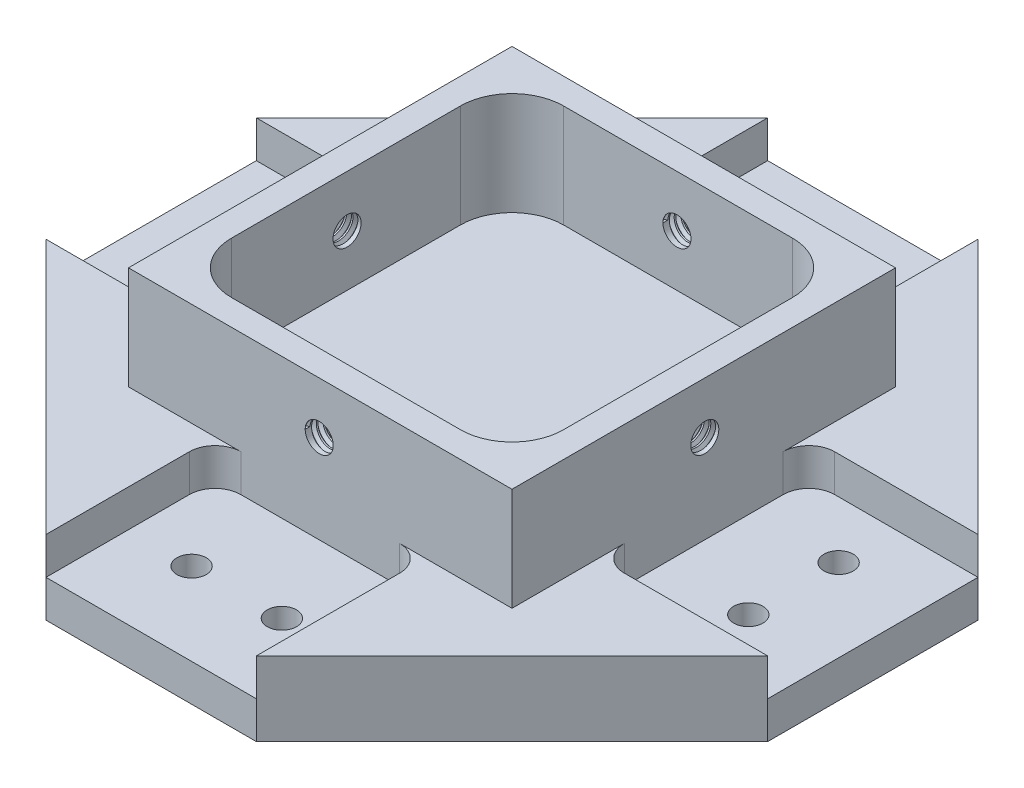
SolidWorks part; units mm, degrees
material "6061 Alloy"
ref_plane "Front Plane" through (0, 0, 0) normal (0, 0, 1) x (1, 0, 0)
ref_plane "Top Plane" through (0, 0, 0) normal (0, 1, 0) x (1, 0, 0)
ref_plane "Right Plane" through (0, 0, 0) normal (1, 0, 0) x (0, 0, -1)
sketch "Sketch1" plane through (0, 0, 0) normal (0, 1, 0) x (1, 0, 0)
  line L1 (0, 0) -> (88.9, 0)
  line L2 (0, 0) -> (0, 88.9)
  line L3 (0, 88.9) -> (88.9, 88.9)
  line L4 (88.9, 0) -> (88.9, 88.9)
  dimension "D1" = 88.9
  dimension "D2" = 88.9
extrude "Boss-Extrude1" add sketch "Sketch1" along normal blind 9.144
sketch "Sketch2" plane through (0, 9.144, 0) normal (0, 1, 0) x (1, 0, 0)
  line L0 (88.9, 88.9) -> (0, 88.9) construction
  line L1 (31.496, 88.9) -> (57.404, 88.9)
  line L2 (31.496, 88.9) -> (31.496, 67.31)
  line L3 (31.496, 67.31) -> (57.404, 67.31)
  line L4 (57.404, 88.9) -> (57.404, 67.31)
  line L5 (0, 88.9) -> (0, 0) construction
  line L6 (0, 57.404) -> (21.59, 57.404)
  line L7 (0, 57.404) -> (0, 31.496)
  line L8 (0, 31.496) -> (21.59, 31.496)
  line L9 (21.59, 57.404) -> (21.59, 31.496)
  line L10 (0, 0) -> (88.9, 0) construction
  line L11 (31.496, 0) -> (57.404, 0)
  line L12 (31.496, 0) -> (31.496, 21.59)
  line L13 (31.496, 21.59) -> (57.404, 21.59)
  line L14 (57.404, 0) -> (57.404, 21.59)
  line L15 (88.9, 0) -> (88.9, 88.9) construction
  line L16 (88.9, 57.404) -> (67.31, 57.404)
  line L17 (88.9, 57.404) -> (88.9, 31.496)
  line L18 (88.9, 31.496) -> (67.31, 31.496)
  line L19 (67.31, 57.404) -> (67.31, 31.496)
  dimension "D1" = 31.496
  dimension "D2" = 25.908
  dimension "D3" = 25.908
  dimension "D4" = 31.496
  dimension "D5" = 25.908
  dimension "D6" = 31.496
  dimension "D7" = 25.908
  dimension "D8" = 31.496
  dimension "D9" = 21.59
  dimension "D10" = 21.59
  dimension "D11" = 21.59
  dimension "D12" = 21.59
extrude "Cut-Extrude1" cut sketch "Sketch2" against normal blind 4.572
sketch "Sketch3" plane through (0, 9.144, 0) normal (0, 1, 0) x (1, 0, 0)
  line L0 (31.496, 88.9) -> (0, 88.9) construction
  line L1 (20.6375, 68.2625) -> (68.2625, 68.2625)
  line L2 (20.6375, 68.2625) -> (20.6375, 20.6375)
  line L3 (20.6375, 20.6375) -> (68.2625, 20.6375)
  line L4 (68.2625, 68.2625) -> (68.2625, 20.6375)
  line L5 (0, 31.496) -> (0, 0) construction
  line L6 (88.9, 31.496) -> (88.9, 57.404) construction
  line L7 (57.404, 88.9) -> (31.496, 88.9) construction
  line L8 (0, 57.404) -> (0, 31.496) construction
  line L9 (31.496, 0) -> (57.404, 0) construction
  circle A0 centre (28.194, 44.45) radius 2.4
  circle A1 centre (44.45, 60.706) radius 2.4
  circle A2 centre (60.706, 44.45) radius 2.4
  circle A3 centre (44.45, 28.194) radius 2.4
  dimension "D5" = 4.8
  dimension "D6" = 4.8
  dimension "D7" = 4.8
  dimension "D8" = 4.8
  dimension "D1" = 47.625
  dimension "D2" = 47.625
  dimension "D3" = 20.6375
  dimension "D4" = 20.6375
  dimension "D9" = 28.194
  dimension "D10" = 28.194
  dimension "D11" = 28.194
  dimension "D12" = 28.194
  dimension "D13" = 23.8125
  dimension "D14" = 23.8125
  dimension "D15" = 23.8125
  dimension "D16" = 23.8125
extrude "Cut-Extrude2" [suppressed] cut sketch "Sketch3" against normal through all contours A2 | A1 | A0 | A3
sketch "Sketch4" plane through (0, 4.572, 0) normal (0, 1, 0) x (1, 0, 0)
  line L0 (0, 57.404) -> (0, 31.496) construction
  line L1 (57.404, 88.9) -> (31.496, 88.9) construction
  line L2 (88.9, 31.496) -> (88.9, 57.404) construction
  line L3 (31.496, 0) -> (57.404, 0) construction
  line L4 (0, 31.496) -> (21.59, 31.496) construction
  line L5 (31.496, 21.59) -> (31.496, 0) construction
  line L6 (67.31, 31.496) -> (88.9, 31.496) construction
  line L7 (57.404, 67.31) -> (57.404, 88.9) construction
  circle A0 centre (78.74, 50.3936) radius 1.8034
  circle A1 centre (78.74, 39.2684) radius 1.8034
  circle A2 centre (49.6316, 78.74) radius 1.8034
  circle A3 centre (38.5064, 78.74) radius 1.8034
  circle A4 centre (10.16, 50.3936) radius 1.8034
  circle A5 centre (10.16, 39.2684) radius 1.8034
  circle A6 centre (39.2684, 10.16) radius 1.8034
  circle A7 centre (50.3936, 10.16) radius 1.8034
  dimension "D1" = 3.6068
  dimension "D2" = 3.6068
  dimension "D3" = 3.6068
  dimension "D4" = 3.6068
  dimension "D5" = 3.6068
  dimension "D6" = 3.6068
  dimension "D7" = 3.6068
  dimension "D8" = 3.6068
  dimension "D9" = 10.16
  dimension "D10" = 10.16
  dimension "D11" = 10.16
  dimension "D12" = 10.16
  dimension "D13" = 10.16
  dimension "D14" = 10.16
  dimension ".313" = 10.16
  dimension "D16" = 10.16
  dimension "D17" = 11.1252
  dimension "D18" = 7.7724
  dimension "D19" = 7.7724
  dimension "D20" = 11.1252
  dimension "D21" = 7.7724
  dimension "D22" = 11.1252
  dimension "D23" = 7.7724
  dimension "D24" = 11.1252
extrude "Cut-Extrude3" cut sketch "Sketch4" against normal through all
sketch "Sketch5" plane through (0, 9.144, 0) normal (0, 1, 0) x (1, 0, 0)
  line L0 (88.9, 88.9) -> (57.404, 88.9) construction
  line L1 (88.9, 31.496) -> (88.9, 57.404) construction
  circle A0 centre (44.45, 44.45) radius 6.35
  dimension "D1" = 12.7
  dimension "D2" = 44.45
  dimension "D3" = 44.45
extrude "Cut-Extrude4" [suppressed] cut sketch "Sketch5" against normal through all
sketch "Sketch6" plane through (0, 9.144, 0) normal (0, 1, 0) x (1, 0, 0)
  line L0 (88.9, 31.496) -> (57.404, 0)
  line L1 (57.404, 0) -> (88.9, 0)
  line L2 (88.9, 0) -> (88.9, 31.496)
extrude "Cut-Extrude5" cut sketch "Sketch6" against normal through all
sketch "Sketch7" plane through (0, 9.144, 0) normal (0, 1, 0) x (1, 0, 0)
  line L0 (0, 88.9) -> (0, 57.404) construction
  line L1 (20.828, 68.072) -> (68.072, 68.072)
  line L2 (20.828, 68.072) -> (20.828, 20.828)
  line L3 (20.828, 20.828) -> (68.072, 20.828)
  line L4 (68.072, 68.072) -> (68.072, 20.828)
  line L5 (0, 0) -> (31.496, 0) construction
  line L7 (24.003, 24.003) -> (64.897, 24.003)
  line L8 (24.003, 24.003) -> (24.003, 64.897)
  line L9 (24.003, 64.897) -> (64.897, 64.897)
  line L10 (64.897, 24.003) -> (64.897, 64.897)
  dimension "D1" = 47.244
  dimension "D2" = 47.244
  dimension "D3" = 20.828
  dimension "D4" = 20.828
  dimension "D5" = 3.175
  dimension "D6" = 3.175
  dimension "D7" = 3.175
  dimension "D8" = 3.175
extrude "Boss-Extrude2" add sketch "Sketch7" along normal blind 12.7 and the other way up to next (4.572 mm away)
fillet "Fillet9" radius 6.35 1 edges at (64.897, 15.494, -24.003)
fillet "Fillet10" radius 6.35 1 edges at (24.003, 15.494, -24.003)
fillet "Fillet11" radius 6.35 1 edges at (64.897, 15.494, -64.897)
fillet "Fillet12" radius 6.35 1 edges at (24.003, 15.494, -64.897)
fillet "Fillet15" radius 3.175 1 edges at (20.828, 6.858, -57.404)
fillet "Fillet16" radius 3.175 1 edges at (31.496, 6.858, -20.828)
fillet "Fillet17" radius 3.175 1 edges at (57.404, 6.858, -20.828)
fillet "Fillet18" radius 3.175 1 edges at (68.072, 6.858, -57.404)
fillet "Fillet19" radius 3.175 1 edges at (68.072, 6.858, -31.496)
fillet "Fillet20" radius 3.175 1 edges at (31.496, 6.858, -68.072)
fillet "Fillet21" radius 3.175 1 edges at (57.404, 6.858, -68.072)
fillet "Fillet22" radius 3.175 1 edges at (20.828, 6.858, -31.496)
sketch "Sketch9" plane through (0, 0, -68.072) normal (0, 0, -1) x (-1, 0, 0)
  line L0 (-68.072, 21.844) -> (-68.072, 9.144) construction
  line L1 (-68.072, 21.844) -> (-20.828, 21.844) construction
  circle A0 centre (-44.323, 15.494) radius 1.7272
  dimension "D1" = 3.4544
  dimension "D2" = 23.749
  dimension "D3" = 6.35
extrude "Cut-Extrude6" cut sketch "Sketch9" against normal through all
sketch "Sketch10" plane through (68.072, 0, 0) normal (1, 0, 0) x (0, 0, -1)
  line L0 (20.828, 21.844) -> (68.072, 21.844) construction
  line L1 (20.828, 21.844) -> (20.828, 9.144) construction
  circle A0 centre (44.577, 15.494) radius 1.7272
  dimension "D1" = 3.4544
  dimension "D2" = 6.35
  dimension "D3" = 23.749
extrude "Cut-Extrude7" cut sketch "Sketch10" against normal through all
sketch "Sketch12" plane through (0, 9.144, 0) normal (0, 1, 0) x (1, 0, 0)
  line L0 (0, 31.496) -> (31.496, 0)
  line L1 (31.496, 0) -> (0, 0)
  line L2 (0, 0) -> (0, 31.496)
  line L3 (57.404, 88.9) -> (88.9, 57.404)
  line L4 (88.9, 57.404) -> (88.9, 88.9)
  line L5 (88.9, 88.9) -> (57.404, 88.9)
  line L6 (0, 57.404) -> (31.496, 88.9)
  line L7 (31.496, 88.9) -> (0, 88.9)
  line L8 (0, 88.9) -> (0, 57.404)
sketch "Sketch14" plane through (0, 0, 0) normal (0, -1, 0) x (1, 0, 0)
  line L0 (60.2924, -60.2924) -> (28.8616, -28.8616) construction
  line L6 (24.003, -58.547) -> (24.003, -30.353) construction
  line L7 (30.353, -24.003) -> (58.547, -24.003) construction
  circle A0 centre (28.8616, -28.8616) radius 2.54
  circle A1 centre (60.2924, -60.2924) radius 2.54
  point P0 (44.577, -44.577)
  dimension "D1" = 44.45
  dimension "D2" = 5.08
  dimension "D3" = 5.08
  dimension "D4" = 20.574
  dimension "D5" = 20.574
extrude "Cut-Extrude9" cut sketch "Sketch14" against normal through all
extrude "Cut-Extrude10" cut sketch "Sketch12" against normal through all
thread "Thread1" pitch 0.7937 method cut profile "Thread Profile1" start angle 0, offset 0, length 0, pitch 0.7937, diameter 3.4544
ref_plane "Plane1" through (42.5958, 15.494, -20.828) normal (0, -1, 0) x (-1, 0, 0)
sketch "Thread Profile1" plane through (42.5958, 15.494, -20.828) normal (0, -1, 0) x (-1, 0, 0)
  line L0 (0, 0) -> (0, 0.7937) construction
  line L1 (0, 0) -> (0.4296, 0.248)
  line L2 (0.4296, 0.248) -> (0.4296, 0.3473)
  line L3 (0.4296, 0.3473) -> (0, 0.5953)
  line L4 (0.4296, 0.2977) -> (0, 0.2977) construction
  line L11 (0, 0) -> (0, 0.5953)
  point P2 (0, 0)
  dimension "Pitch" = 0.7937
  dimension "Profile_Angle" = 60
  dimension "Profile_Land" = 0.0992
  dimension "Profile_Height" = 0.4296
thread "Thread2" pitch 0.7937 method cut profile "Thread Profile2" start angle 0, offset 0, length 0, pitch 0.7937, diameter 3.4544
ref_plane "Plane2" through (68.072, 15.494, -42.8498) normal (0, -1, 0) x (0, 0, 1)
sketch "Thread Profile2" plane through (68.072, 15.494, -42.8498) normal (0, -1, 0) x (0, 0, 1)
  line L0 (0, 0) -> (0, 0.7937) construction
  line L1 (0, 0) -> (0.4296, 0.248)
  line L2 (0.4296, 0.248) -> (0.4296, 0.3473)
  line L3 (0.4296, 0.3473) -> (0, 0.5953)
  line L4 (0.4296, 0.2977) -> (0, 0.2977) construction
  line L11 (0, 0) -> (0, 0.5953)
  point P2 (0, 0)
  dimension "Pitch" = 0.7937
  dimension "Profile_Angle" = 60
  dimension "Profile_Land" = 0.0992
  dimension "Profile_Height" = 0.4296
thread "Thread3" pitch 0.7937 method cut profile "Thread Profile3" start angle 0, offset 0, length 0, pitch 0.7937, diameter 3.4544
ref_plane "Plane3" through (42.5958, 15.494, -64.897) normal (0, -1, 0) x (-1, 0, 0)
sketch "Thread Profile3" plane through (42.5958, 15.494, -64.897) normal (0, -1, 0) x (-1, 0, 0)
  line L0 (0, 0) -> (0, 0.7937) construction
  line L1 (0, 0) -> (0.4296, 0.248)
  line L2 (0.4296, 0.248) -> (0.4296, 0.3473)
  line L3 (0.4296, 0.3473) -> (0, 0.5953)
  line L4 (0.4296, 0.2977) -> (0, 0.2977) construction
  line L11 (0, 0) -> (0, 0.5953)
  point P2 (0, 0)
  dimension "Pitch" = 0.7937
  dimension "Profile_Angle" = 60
  dimension "Profile_Land" = 0.0992
  dimension "Profile_Height" = 0.4296
thread "Thread4" pitch 0.7937 method cut profile "Thread Profile4" start angle 0, offset 0, length 0, pitch 0.7937, diameter 3.4544
ref_plane "Plane4" through (24.003, 15.494, -42.8498) normal (0, -1, 0) x (0, 0, 1)
sketch "Thread Profile4" plane through (24.003, 15.494, -42.8498) normal (0, -1, 0) x (0, 0, 1)
  line L0 (0, 0) -> (0, 0.7937) construction
  line L1 (0, 0) -> (0.4296, 0.248)
  line L2 (0.4296, 0.248) -> (0.4296, 0.3473)
  line L3 (0.4296, 0.3473) -> (0, 0.5953)
  line L4 (0.4296, 0.2977) -> (0, 0.2977) construction
  line L11 (0, 0) -> (0, 0.5953)
  point P2 (0, 0)
  dimension "Pitch" = 0.7937
  dimension "Profile_Angle" = 60
  dimension "Profile_Land" = 0.0992
  dimension "Profile_Height" = 0.4296
equation "\"hinge_hole\"= 0.142in"
equation "\"D1@Sketch4\"=\"hinge_hole\""
equation "\"D2@Sketch4\"=\"hinge_hole\""
equation "\"D3@Sketch4\"=\"hinge_hole\""
equation "\"D4@Sketch4\"=\"hinge_hole\""
equation "\"D5@Sketch4\"=\"hinge_hole\""
equation "\"D6@Sketch4\"=\"hinge_hole\""
equation "\"D7@Sketch4\"=\"hinge_hole\""
equation "\"D8@Sketch4\"=\"hinge_hole\""
equation "\"hinge_hole_dist\"= 0.297 + 0.25"
equation "\"hinge_hole_sep\"=0.438"
equation "\"hinge_hole_from_wall\"= ( 1.05 - .438 ) / 2"
equation "\"D17@Sketch4\"=\"hinge_hole_sep\""
equation "\"D18@Sketch4\"=\"hinge_hole_from_wall\""
equation "\"D19@Sketch4\"=\"hinge_hole_from_wall\""
equation "\"D20@Sketch4\"=\"hinge_hole_sep\""
equation "\"D21@Sketch4\"=\"hinge_hole_from_wall\""
equation "\"D22@Sketch4\"=\"hinge_hole_sep\""
equation "\"D23@Sketch4\"=\"hinge_hole_from_wall\""
equation "\"D24@Sketch4\"=\"hinge_hole_sep\""
equation "\"D9@Sketch2\"=\"hinge_hole_dist\" + (0.6-0.297)"
equation "\"D12@Sketch2\"=\"hinge_hole_dist\" + (0.6-0.297)"
equation "\"D11@Sketch2\"=\"hinge_hole_dist\" + (0.6-0.297)"
equation "\"D10@Sketch2\"=\"hinge_hole_dist\" + (0.6-0.297)"
equation "\"Hinge_hole_inset\"=0.4"
equation "\"D14@Sketch4\"=\"Hinge_hole_inset\""
equation "\"D13@Sketch4\"=\"Hinge_hole_inset\""
equation "\"D12@Sketch4\"=\"Hinge_hole_inset\""
equation "\"D11@Sketch4\"=\"Hinge_hole_inset\""
equation "\"D10@Sketch4\"=\"Hinge_hole_inset\""
equation "\"D9@Sketch4\"=\"Hinge_hole_inset\""
equation "\"D16@Sketch4\"=\"Hinge_hole_inset\""
equation "\".313@Sketch4\"=\"Hinge_hole_inset\""
